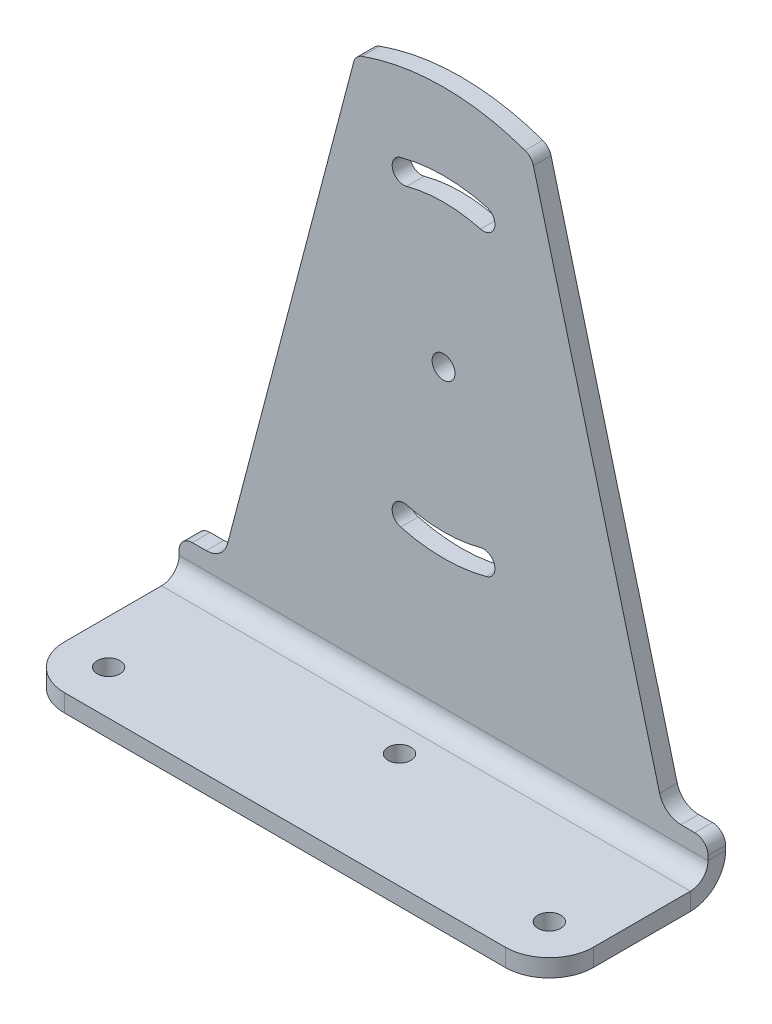
SolidWorks part; units mm, degrees
note: The reader was unsure of these and kept them because the rebuilt part matched: thickness of "Базовая кромка2", "Ребро-кромка2", "Листовой металл6", "Листовой металл7", "Листовой металл8"; flange length of "Ребро-кромка2".
ref_plane "Спереди" through (0, 0, 0) normal (0, 0, 1) x (1, 0, 0)
ref_plane "Сверху" through (0, 0, 0) normal (0, 1, 0) x (1, 0, 0)
ref_plane "Справа" through (0, 0, 0) normal (1, 0, 0) x (0, 0, -1)
sketch "Эскиз13" plane through (0, 0, 0) normal (0, 0, 1) x (1, 0, 0)
  line L0 (-60, 0) -> (60, 0)
  line L1 (50, 12) -> (20, 126.2348)
  line L2 (20, 126.2348) -> (-20, 126.2348) construction
  line L3 (-20, 126.2348) -> (-50, 12)
  line L4 (0, 0) -> (0, 75) construction
  line L5 (0, 75) -> (9.0587, 108.8074) construction
  line L6 (-60, 0) -> (-60, 12)
  line L7 (-60, 12) -> (-50, 12)
  line L8 (60, 0) -> (60, 12)
  line L9 (60, 12) -> (50, 12)
  circle A0 centre (0, 75) radius 2.6
  arc A1 (-9.0587, 108.8074) -> (9.0587, 108.8074) centre (0, 75) cw construction
  arc A2 (9.7316, 111.3188) -> (-9.7316, 111.3188) centre (0, 75) ccw
  arc A3 (8.3857, 106.296) -> (-8.3857, 106.296) centre (0, 75) ccw
  arc A4 (8.3857, 106.296) -> (9.7316, 111.3188) centre (9.0587, 108.8074) ccw
  arc A5 (-9.7316, 111.3188) -> (-8.3857, 106.296) centre (-9.0587, 108.8074) ccw
  arc A6 (-9.0587, 41.1926) -> (9.0587, 41.1926) centre (0, 75) ccw construction
  arc A7 (-9.7316, 38.6812) -> (9.7316, 38.6812) centre (0, 75) ccw
  arc A8 (-8.3857, 43.704) -> (8.3857, 43.704) centre (0, 75) ccw
  arc A9 (-8.3857, 43.704) -> (-9.7316, 38.6812) centre (-9.0587, 41.1926) ccw
  arc A10 (9.7316, 38.6812) -> (8.3857, 43.704) centre (9.0587, 41.1926) ccw
  arc A11 (-20, 126.2348) -> (20, 126.2348) centre (0, 75) cw
  point P7 (0, 110)
  point P16 (0, 40)
  point P25 (0, 130)
  dimension "D7" = 40
  dimension "D3" = 2.6
  dimension "D4" = 35
  dimension "D5" = 5.2
  dimension "D1" = 75
  dimension "D2" = 15
  dimension "D6" = 20
  dimension "D8" = 120
  dimension "D9" = 10
  dimension "D10" = 12
base flange "Базовая кромка2" sketch "Эскиз13" thickness 4 reverse thickness direction no parameters "D1"=4
edge flange "Ребро-кромка2" sketch "Эскиз22" flange angle 90 flange length 40 flange position material inside bend radius 4 thickness 4 relief rectangular parameters "D1"=0.7366, "D6"=10
sketch "Эскиз22" plane through (0, 0, 0) normal (0, -1, 0) x (1, 0, 0)
  line L2 (-60, 0) -> (-60, 36)
  line L3 (-60, 36) -> (60, 36)
  line L4 (60, 36) -> (60, 0)
  line L7 (-60, 0) -> (60, 0) construction
  line L8 (-60, 0) -> (60, 0)
bend "EdgeBend3" bend radius 4 bend angle 90 parameters "D5"=1
fillet "Скругление1" radius 5 2 edges at (-50, 12, -2) (50, 12, -2)
fillet "Скругление2" radius 3 4 edges at (60, 12, -2) (-60, 12, -2) (20, 126.2348, -2) (-20, 126.2348, -2)
fillet "Скругление3" radius 10 2 edges at (60, 2, 36) (-60, 2, 36)
sketch "Эскиз23" plane through (0, 4, 0) normal (0, 1, 0) x (1, 0, 0)
  circle A0 centre (-50, -26) radius 2.6
  circle A1 centre (50, -26) radius 2.6
  circle A2 centre (0, -10) radius 2.6
  dimension "D2" = 5.2
  dimension "D1" = 10
extrude "Вырез-Вытянуть2" cut sketch "Эскиз23" against normal blind 10 normal cut yes
sketch "Сгиб-Линии3" [suppressed] plane through (0, 0, 0) normal (0, 1, 0) x (1, 0, 0)
sketch "Граничная рамка3" [suppressed] plane through (0, 0, 0) normal (0, 1, 0) x (1, 0, 0)
sheet metal parameters "Листовой металл6" thickness 4 parameters "D1"=0.7366, "D7"=3
flat pattern "Развертка6" [suppressed]
sketch "Сгиб-Линии4" plane through (0, 0, 0) normal (0, 1, 0) x (1, 0, 0)
sketch "Граничная рамка4" [suppressed] plane through (0, 0, 0) normal (0, 1, 0) x (1, 0, 0)
sheet metal parameters "Листовой металл7" thickness 4 parameters "D1"=0.7366, "D7"=3
flat pattern "Развертка6" [suppressed]
sketch "Сгиб-Линии4" plane through (0, 0, 0) normal (0, 1, 0) x (1, 0, 0)
sketch "Граничная рамка4" [suppressed] plane through (0, 0, 0) normal (0, 1, 0) x (1, 0, 0)
bend of the flat pattern "Плоское состояние-<EdgeBend3>1"
sheet metal parameters "Листовой металл8" thickness 4 parameters "D1"=0.7366, "D7"=3
flat pattern "Развертка6"
sketch "Сгиб-Линии4" plane through (0, 0, 0) normal (0, 0, 1) x (1, 0, 0)
  line L0 (-60, 3.2876) -> (60, 3.2876) construction
  line L1 (-60, 3.2876) -> (60, 3.2876) construction
sketch3d "Граничная рамка4" [suppressed]
  line L0 (60, 55, 0) -> (60, -108.4248, 0) construction
  line L1 (-60, 55, 0) -> (-60, -108.4248, 0) construction
  line L2 (60, 55, 0) -> (-60, 55, 0) construction
  line L3 (60, -108.4248, 0) -> (-60, -108.4248, 0) construction
bend of the flat pattern "Плоское состояние-<EdgeBend3>1"
